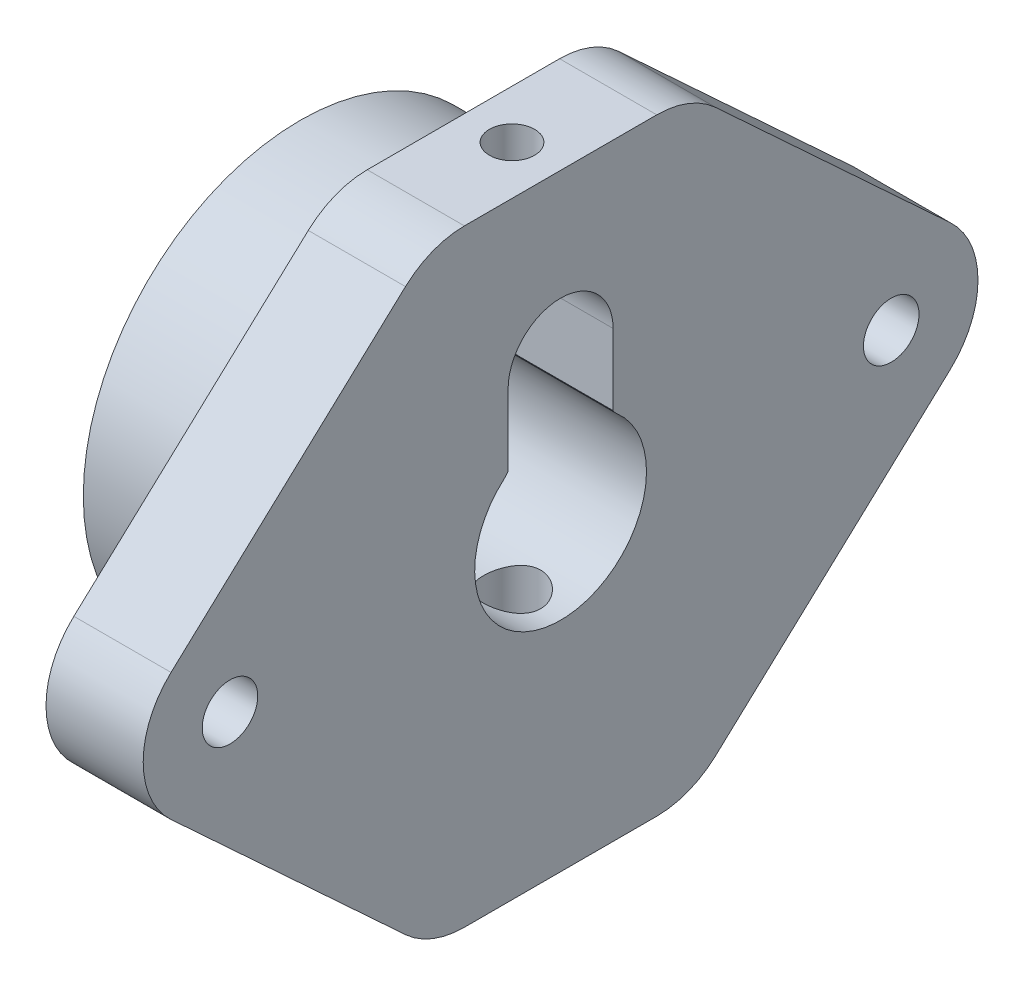
SolidWorks part; units mm, degrees
material "5052-H34"
ref_plane "正面" through (0, 0, 0) normal (0, 0, 1) x (1, 0, 0)
ref_plane "平面" through (0, 0, 0) normal (0, 1, 0) x (1, 0, 0)
ref_plane "右側面" through (0, 0, 0) normal (1, 0, 0) x (0, 0, -1)
sketch "ｽｹｯﾁ1" plane through (0, 0, 0) normal (1, 0, 0) x (0, 0, -1)
  circle A0 centre (0, 0) radius 12.5
  dimension "D1" = 25
extrude "ﾎﾞｽ - 押し出し1" add sketch "ｽｹｯﾁ1" along normal blind 15
sketch "ｽｹｯﾁ2" plane through (15, 0, 0) normal (1, 0, 0) x (0, 0, -1)
  circle A0 centre (0, 0) radius 25
  dimension "D1" = 50
extrude "ﾎﾞｽ - 押し出し2" add sketch "ｽｹｯﾁ2" against normal blind 5.6
sketch "ｽｹｯﾁ3" plane through (15, 0, 0) normal (1, 0, 0) x (0, 0, -1)
  circle A0 centre (0, 0) radius 4.95
  dimension "D1" = 9.9
extrude "ｶｯﾄ - 押し出し1" cut sketch "ｽｹｯﾁ3" against normal through all
sketch "ｽｹｯﾁ4" plane through (15, 0, 0) normal (1, 0, 0) x (0, 0, -1)
  line L0 (0, 0) -> (25, 0) construction
  line L1 (0, 0) -> (0, 17.5) construction
  line L2 (17.8536, 17.5) -> (-17.8536, 17.5)
  line L3 (17.8536, -17.5) -> (-17.8536, -17.5)
  circle A0 centre (0, 0) radius 25 construction
  circle A1 centre (0, 0) radius 17.5 construction
  circle M5 centre (0, 0) radius 25
  dimension "D1" = 7.5
extrude "ｶｯﾄ - 押し出し2" cut sketch "ｽｹｯﾁ4" against normal through all contours L2 M5 | L3 M5 region at (15, 20.5423, 0) region at (15, -20.5423, 0)
sketch "ｽｹｯﾁ5" plane through (0, 17.5, 0) normal (0, 1, 0) x (1, 0, 0)
  line L0 (9.4, 0) -> (15, 0) construction
  line L1 (15, 17.8536) -> (15, -17.8536) construction
  line L2 (9.4, 17.8536) -> (9.4, -17.8536) construction
  circle A0 centre (12.2, 0) radius 1.3
  dimension "D1" = 2.6
extrude "ｶｯﾄ - 押し出し3" cut sketch "ｽｹｯﾁ5" against normal through all
sketch "ｽｹｯﾁ6" plane through (15, 0, 0) normal (1, 0, 0) x (0, 0, -1)
  line L0 (0, 0) -> (0, 17.5) construction
  line L1 (17.8536, 17.5) -> (-17.8536, 17.5) construction
  line L2 (0, 0) -> (-19.05, 0) construction
  circle A0 centre (-19.05, 0) radius 1.6
  circle A1 centre (19.05, 0) radius 1.6
  dimension "D1" = 3.2
  dimension "D2" = 38.1
extrude "ｶｯﾄ - 押し出し4" cut sketch "ｽｹｯﾁ6" against normal through all
sketch "ｽｹｯﾁ7" plane through (9.4, 0, 0) normal (-1, 0, 0) x (0, 0, 1)
  circle A0 centre (0, 0) radius 13.5
  circle A1 centre (0, 0) radius 12.5
  circle A2 centre (0, 0) radius 12.5
  dimension "D1" = 0
  dimension "D2" = 1
extrude "ﾎﾞｽ - 押し出し3" add sketch "ｽｹｯﾁ7" along normal blind 0.5
sketch "ｽｹｯﾁ9" plane through (15, 0, 0) normal (1, 0, 0) x (0, 0, -1)
  line L0 (17.8536, 17.5) -> (-17.8536, 17.5) construction
  line L1 (-7.5, -17.5) -> (7.5, -17.5)
  line L2 (-7.5, -17.5) -> (-7.5, 17.5)
  line L3 (-7.5, 17.5) -> (7.5, 17.5)
  line L4 (7.5, -17.5) -> (7.5, 17.5)
  line L5 (-7.5, -17.5) -> (7.5, 17.5) construction
  line L6 (-7.5, 17.5) -> (7.5, -17.5) construction
  line L7 (-7.5, 17.5) -> (-22.4459, 3.6699)
  line L8 (0, 0) -> (0, 17.5) construction
  line L9 (0, 0) -> (7.5, 0) construction
  line L10 (7.5, 17.5) -> (22.4459, 3.6699)
  line L11 (7.5, -17.5) -> (22.4459, -3.6699)
  line L12 (-7.5, -17.5) -> (-22.4459, -3.6699)
  circle A0 centre (-19.05, 0) radius 5
  circle A1 centre (0, 0) radius 4.95
  circle A2 centre (0, 0) radius 4.95
  circle A3 centre (19.05, 0) radius 1.6
  circle A4 centre (19.05, 0) radius 1.6
  circle A5 centre (-19.05, 0) radius 1.6
  circle A6 centre (-19.05, 0) radius 1.6
  circle A7 centre (19.05, 0) radius 5
  arc M12 (17.8536, -17.5) -> (17.8536, 17.5) centre (0, 0) ccw
  line M13 (17.8536, 17.5) -> (-17.8536, 17.5)
  arc M14 (-17.8536, 17.5) -> (-17.8536, -17.5) centre (0, 0) ccw
  line M15 (-17.8536, -17.5) -> (17.8536, -17.5)
  dimension "D4" = 10
  dimension "D5" = 15
  dimension "D1" = 0
  dimension "D2" = 0
  dimension "D3" = 0
extrude "ｶｯﾄ - 押し出し6" cut sketch "ｽｹｯﾁ9" against normal through all contours A0 L7 L12 M13 M14 M15 | A7 L11 L10 M15 M12 M13 region at (15, -17.1087, 12.6768) region at (15, -10.8721, -15.2387)
sketch "ｽｹｯﾁ10" plane through (15, 0, 0) normal (1, 0, 0) x (0, 0, -1)
  line L0 (0, 0) -> (0, 8.1) construction
  line L2 (-3.025, 4) -> (3.025, 4)
  line L3 (-3.025, 4) -> (-3.025, 8.1)
  line L5 (3.025, 4) -> (3.025, 8.1)
  arc A1 (3.025, 8.1) -> (-3.025, 8.1) centre (0, 8.1) ccw
  dimension "D1" = 6.05
  dimension "D2" = 4.1
  dimension "D3" = 4
extrude "ｶｯﾄ - 押し出し7" cut sketch "ｽｹｯﾁ10" against normal up to surface (15 mm away) up to face at (0, 0, -4.95)
fillet "ﾌｨﾚｯﾄ3" radius 5 4 edges at (12.2, -17.5, -7.5) (12.2, -17.5, 7.5) (12.2, 17.5, -7.5) (12.2, 17.5, 7.5)
fillet "ﾌｨﾚｯﾄ4" radius 1 2 edges at (7.5, 4, 2.9159) (7.5, 4, -2.9159)
sketch "ｽｹｯﾁ11" plane through (0, -17.5, 0) normal (0, -1, 0) x (1, 0, 0)
  circle A0 centre (12.2, 0) radius 1.3 construction
  circle A1 centre (12.2, 0) radius 1.3
  circle A2 centre (12.2, 0) radius 1.65
  dimension "D1" = 3.3
extrude "ｶｯﾄ - 押し出し8" cut sketch "ｽｹｯﾁ11" against normal blind 15
